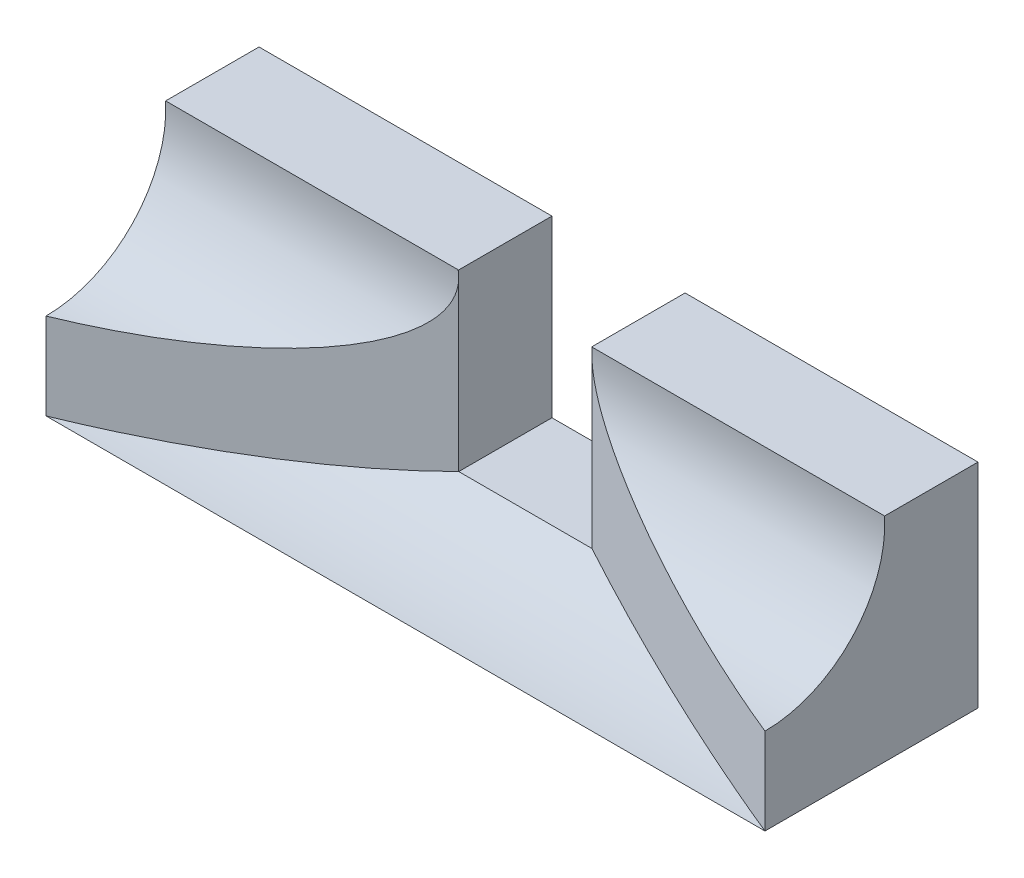
SolidWorks part; units mm, degrees
ref_plane "Front Plane" through (0, 0, 0) normal (0, 0, 1) x (1, 0, 0)
ref_plane "Top Plane" through (0, 0, 0) normal (0, 1, 0) x (1, 0, 0)
ref_plane "Right Plane" through (0, 0, 0) normal (1, 0, 0) x (0, 0, -1)
sketch "Sketch1" plane through (0, 0, 0) normal (0, 1, 0) x (1, 0, 0)
  line L1 (-135, 40) -> (135, 40)
  line L2 (-135, 40) -> (-135, -40)
  line L3 (-135, -40) -> (135, -40)
  line L4 (135, 40) -> (135, -40)
  line L5 (-135, 40) -> (135, -40) construction
  line L6 (-135, -40) -> (135, 40) construction
  point P0 (0, 0)
  dimension "D1" = 270
  dimension "D2" = 80
extrude "Boss-Extrude1" add sketch "Sketch1" along normal blind 80
sketch "Sketch2" plane through (0, 80, 0) normal (0, 1, 0) x (1, 0, 0)
  line L0 (0, 40) -> (0, -40) construction
  line L1 (135, 40) -> (-135, 40) construction
  line L2 (-135, -40) -> (135, -40) construction
  line L3 (25, 5) -> (-25, 5)
  line L4 (-25, 5) -> (-135, -40)
  line L5 (-135, -40) -> (135, -40)
  line L6 (0, -40) -> (0, 5)
  line L7 (25, 5) -> (135, -40)
  line M4 (-135, -40) -> (135, -40)
  dimension "D1" = 45
  dimension "D2" = 50
extrude "Cut-Extrude1" cut sketch "Sketch2" against normal through all contours L6 L3 L4 M4 | L7 L3 L6 L5 region at (46.3021, 80, 22.6562) region at (-46.3021, 80, 22.6562)
sketch "Sketch4" plane through (135, 0, 0) normal (1, 0, 0) x (0, 0, -1)
  line L0 (-40, 80) -> (-40, 0) construction
  line L1 (-40, 0) -> (40, 0) construction
  line L2 (40, 80) -> (37.4597, 80)
  line L3 (40, 80) -> (40, 0)
  line L4 (40, 0) -> (-40, 0)
  arc A0 (-40, 0) -> (37.4597, 80) centre (-40, 77.5) ccw
  circle A1 centre (-40, 77.5) radius 40 construction
  point P9 (-40, 37.5)
  dimension "D1" = 80
  dimension "D2" = 37.5
extrude "Boss-Extrude2" add sketch "Sketch4" against normal up to surface (270 mm away) up to face at (-135, 40, 0)
sketch "Sketch3" plane through (135, 0, 0) normal (1, 0, 0) x (0, 0, -1)
  line L3 (-40, 80) -> (-40, 0) construction
  circle A0 centre (-40, 77.5) radius 40 construction
  circle A1 centre (-40, 77.5) radius 45
  point P2 (-40, 37.5)
  dimension "D1" = 80
  dimension "D2" = 90
  dimension "D3" = 37.5
extrude "Cut-Extrude2" cut sketch "Sketch3" against normal through all
sketch "Sketch5" plane through (0, 0, -5) normal (0, 0, 1) x (1, 0, 0)
  line L1 (-25, 14.4029) -> (25, 14.4029)
  line L2 (-25, 14.4029) -> (-25, 80)
  line L3 (-25, 80) -> (25, 80)
  line L4 (25, 14.4029) -> (25, 80)
extrude "Cut-Extrude3" cut sketch "Sketch5" against normal through all
